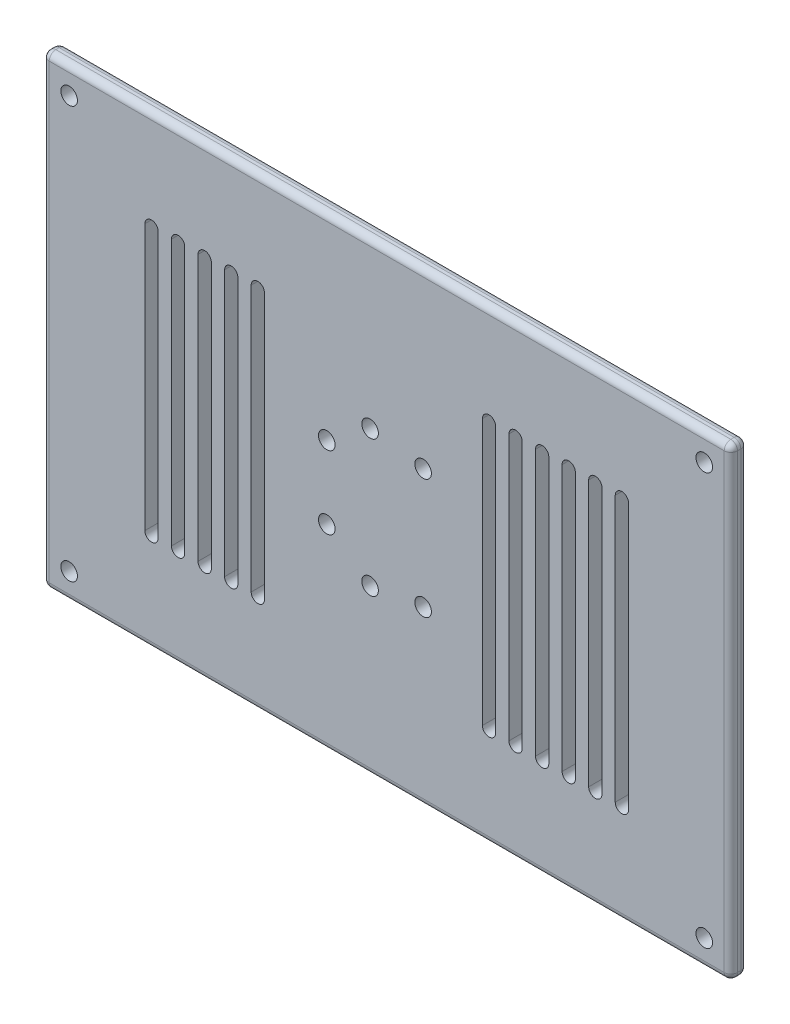
SolidWorks part; units mm, degrees
ref_plane "Plan de face" through (0, 0, 0) normal (0, 0, 1) x (1, 0, 0)
ref_plane "Plan de dessus" through (0, 0, 0) normal (0, 1, 0) x (1, 0, 0)
ref_plane "Plan de droite" through (0, 0, 0) normal (1, 0, 0) x (0, 0, -1)
sketch "Esquisse1" plane through (0, 0, 0) normal (0, 0, 1) x (1, 0, 0)
  line L1 (-51.8, 35) -> (51.8, 35)
  line L2 (-51.8, 35) -> (-51.8, -35)
  line L3 (-51.8, -35) -> (51.8, -35)
  line L4 (51.8, 35) -> (51.8, -35)
  line L5 (-51.8, 35) -> (51.8, -35) construction
  line L6 (-51.8, -35) -> (51.8, 35) construction
  point P0 (0, 0)
  point P5 (0, 0)
  point P13 (0, 0)
  dimension "D1" = 70
  dimension "D2" = 103.6
extrude "Boss.-Extru.1" add sketch "Esquisse1" along normal blind 2.5
sketch "Esquisse17" plane through (0, 0, 2.5) normal (0, 0, 1) x (1, 0, 0)
  line L1 (-2.5, 10.25) -> (2.5, 10.25)
  line L2 (-2.5, 10.25) -> (-2.5, -10.25) construction
  line L3 (-2.5, -10.25) -> (2.5, -10.25)
  line L4 (2.5, 10.25) -> (2.5, -10.25)
  line L5 (-2.5, 10.25) -> (2.5, -10.25) construction
  line L6 (-2.5, -10.25) -> (2.5, 10.25) construction
  circle A0 centre (-2.5, 10.25) radius 3
  circle A1 centre (-2.5, -10.25) radius 3
  point P0 (0, 0)
  point P9 (-2.5, -10.25)
  point P10 (-2.5, 10.25)
  dimension "D1" = 20.5
  dimension "D2" = 5
fillet "Congé3" radius 1 12 edges at (-51.8, 0, 2.5) (0, -35, 2.5) (0, 35, 2.5) (51.8, 0, 2.5) (51.8, -35, 1.25) (51.8, 35, 1.25) (-51.8, 35, 1.25) (-51.8, -35, 1.25) (51.8, 0, 0) (0, 35, 0) (-51.8, 0, 0) (0, -35, 0)
extrude "Boss.-Extru.12" add sketch "Esquisse17" against normal blind 7 contours A1 | A0
sketch "Esquisse40" plane through (0, 0, 2.5) normal (0, 0, 1) x (1, 0, 0)
  line L1 (9.0156, -5.4801) -> (5.4801, -9.0156)
  line L2 (9.0156, -5.4801) -> (-5.4801, 9.0156)
  line L3 (-5.4801, 9.0156) -> (-9.0156, 5.4801)
  line L4 (5.4801, -9.0156) -> (-9.0156, 5.4801)
  line L5 (2.5, -10.25) -> (-2.5, 10.25) construction
  line L6 (2.5, 10.25) -> (-2.5, -10.25) construction
  circle A0 centre (5.4801, -9.0156) radius 3
  circle A1 centre (-9.0156, 5.4801) radius 3
  point P0 (0, 0)
  dimension "D1" = 5
  dimension "D2" = 20.5
extrude "Boss.-Extru.8" add sketch "Esquisse40" against normal blind 7 contours A1 | A0
sketch "Esquisse42" plane through (0, 0, 2.5) normal (0, 0, 1) x (1, 0, 0)
  line L5 (-5.4801, -9.0156) -> (-9.0156, -5.4801)
  line L6 (-5.4801, -9.0156) -> (9.0156, 5.4801)
  line L7 (9.0156, 5.4801) -> (5.4801, 9.0156)
  line L8 (-9.0156, -5.4801) -> (5.4801, 9.0156)
  line L9 (2.5, -10.25) -> (-2.5, 10.25) construction
  line L10 (2.5, 10.25) -> (-2.5, -10.25) construction
  circle A0 centre (-9.0156, -5.4801) radius 3
  circle A1 centre (5.4801, 9.0156) radius 3
  point P0 (0, 0)
  dimension "D1" = 5
  dimension "D2" = 20.5
extrude "Boss.-Extru.10" add sketch "Esquisse42" against normal blind 7 contours A1 | A0
sketch "Esquisse36" plane through (0, 0, 2.5) normal (0, 0, 1) x (1, 0, 0)
  line L0 (25.4, 0) -> (0, 0) construction
  line L1 (50.8, -34) -> (50.8, 34) construction
  line L2 (50.8, 0) -> (25.4, 0) construction
  line L4 (35.4, -20) -> (15.4, -20) construction
  line L5 (35.4, -20) -> (35.4, 20) construction
  line L6 (35.4, 20) -> (15.4, 20) construction
  line L7 (15.4, -20) -> (15.4, 20) construction
  line L8 (35.4, -20) -> (15.4, 20) construction
  line L9 (35.4, 20) -> (15.4, -20) construction
  line L10 (35.4, 20) -> (35.4, -20) construction
  line L11 (36.4, 20) -> (36.4, -20)
  line L12 (34.4, 20) -> (34.4, -20)
  arc A0 (36.4, 20) -> (34.4, 20) centre (35.4, 20) ccw
  arc A1 (34.4, -20) -> (36.4, -20) centre (35.4, -20) ccw
  point P0 (25.4, 0)
  point P8 (35.4, 0)
  dimension "D1" = 20
  dimension "D2" = 40
extrude "Enlèv. mat.-Extru.2" cut sketch "Esquisse36" against normal through all
pattern_linear "Répétition linéaire1" count 6 spacing 4 along (-1, 0, 0) of "Enlèv. mat.-Extru.2"
sketch "Esquisse37" plane through (0, 0, 2.5) normal (0, 0, 1) x (1, 0, 0)
  line L0 (0, 0) -> (-50.8, 0) construction
  line L1 (-50.8, 34) -> (-50.8, -34) construction
  line L2 (-35.4, 20) -> (-35.4, -20) construction
  line L3 (-15.4, 20) -> (-35.4, 20) construction
  line L4 (-15.4, 20) -> (-15.4, -20) construction
  line L5 (-15.4, -20) -> (-35.4, -20) construction
  line L6 (-35.4, 20) -> (-35.4, -20) construction
  line L7 (-15.4, 20) -> (-35.4, -20) construction
  line L8 (-15.4, -20) -> (-35.4, 20) construction
  line L9 (-34.4, 20) -> (-34.4, -20)
  line L10 (-36.4, 20) -> (-36.4, -20)
  arc A0 (-34.4, 20) -> (-36.4, 20) centre (-35.4, 20) ccw
  arc A1 (-36.4, -20) -> (-34.4, -20) centre (-35.4, -20) ccw
  point P5 (-25.4, 0)
  point P11 (-35.4, 0)
  dimension "D1" = 40
  dimension "D2" = 20
extrude "Enlèv. mat.-Extru.3" cut sketch "Esquisse37" against normal through all
pattern_linear "Répétition linéaire2" count 5 spacing 4 along (1, 0, 0) of "Enlèv. mat.-Extru.3"
hole_wizard "Trou pour taraudage pour trou taraudé M38" positions "Esquisse3D10" profile "Esquisse41" hole size "M3" standard "AS"
sketch3d "Esquisse3D10"
  point P0 (5.4801, -9.0156, 2.5)
  point P3 (-9.0156, 5.4801, 2.5)
sketch "Esquisse41" plane through (5.4801, -9.0156, 2.5) normal (1, 0, 0) x (0, -1, 0)
  line L0 (0, 0) -> (0, 7.7511)
  line L1 (0, 7.7511) -> (1.25, 7)
  line L2 (1.25, 7) -> (1.25, 0)
  line L5 (1.25, 0) -> (0, 0)
  line L10 (0, 7.7511) -> (-1.25, 7) construction
  line L11 (0, -6.35) -> (0, 107.95) construction
  dimension "Diamètre du perçage" = 2.5
  dimension "Profondeur du perçage" = 7
  dimension "Angle de pointe" = 118
hole_wizard "Trou pour taraudage pour trou taraudé M39" positions "Esquisse3D11" profile "Esquisse43" hole size "M3" standard "AS"
sketch3d "Esquisse3D11"
  point P0 (5.4801, 9.0156, 2.5)
  point P3 (-9.0156, -5.4801, 2.5)
sketch "Esquisse43" plane through (5.4801, 9.0156, 2.5) normal (1, 0, 0) x (0, -1, 0)
  line L0 (0, 0) -> (0, 7.7511)
  line L1 (0, 7.7511) -> (1.25, 7)
  line L2 (1.25, 7) -> (1.25, 0)
  line L5 (1.25, 0) -> (0, 0)
  line L10 (0, 7.7511) -> (-1.25, 7) construction
  line L11 (0, -6.35) -> (0, 107.95) construction
  dimension "Diamètre du perçage" = 2.5
  dimension "Profondeur du perçage" = 7
  dimension "Angle de pointe" = 118
hole_wizard "Trou pour taraudage pour trou taraudé M311" positions "Esquisse3D15" profile "Esquisse47" hole size "M3" standard "AS"
sketch3d "Esquisse3D15"
  point P0 (-2.5, 10.25, 2.5)
  point P3 (-2.5, -10.25, 2.5)
sketch "Esquisse47" plane through (-2.5, 10.25, 2.5) normal (1, 0, 0) x (0, -1, 0)
  line L0 (0, 0) -> (0, 7.7511)
  line L1 (0, 7.7511) -> (1.25, 7)
  line L2 (1.25, 7) -> (1.25, 0)
  line L5 (1.25, 0) -> (0, 0)
  line L10 (0, 7.7511) -> (-1.25, 7) construction
  line L11 (0, -6.35) -> (0, 107.95) construction
  dimension "Diamètre du perçage" = 2.5
  dimension "Profondeur du perçage" = 7
  dimension "Angle de pointe" = 118
fillet "Congé4" radius 0.5 18 edges at (0.5, -10.25, 0) (0.5, -10.25, -4.5) (0.5, 10.25, 0) (0.5, 10.25, -4.5) (8.4801, -9.0156, -4.5) (8.4801, 9.0156, -4.5) (-6.0156, 5.4801, 0) (-6.0156, 5.4801, -4.5) (-6.0156, -5.4801, 0) (-6.0156, -5.4801, -4.5) (8.4801, 9.0156, 0) (8.4801, -9.0156, 0) (6.7301, -9.0156, -4.5) (6.7301, 9.0156, -4.5) (-1.25, -10.25, -4.5) (-1.25, 10.25, -4.5) (-7.7656, -5.4801, -4.5) (-7.7656, 5.4801, -4.5)
sketch "Esquisse48" plane through (0, 0, 2.5) normal (0, 0, 1) x (1, 0, 0)
  line L0 (51.8, 34) -> (51.8, -34) construction
  line L1 (-50.8, 35) -> (50.8, 35) construction
  line L2 (50.8, -35) -> (-50.8, -35) construction
  line L3 (-50.8, -35) -> (50.8, -35) construction
  line L6 (-51.8, -34) -> (-51.8, 34) construction
  circle A0 centre (-47.8, 31) radius 3
  circle A1 centre (-47.8, -31) radius 3
  circle A2 centre (47.8, 31) radius 3.3164
  circle A3 centre (47.8, -31) radius 3.4515
  dimension "D1" = 4
  dimension "D2" = 4
  dimension "D3" = 4
  dimension "D4" = 4
  dimension "D5" = 4
  dimension "D6" = 4
  dimension "D7" = 4
  dimension "D8" = 4
hole_wizard "Trou pour taraudage pour trou taraudé M312" positions "Esquisse3D16" profile "Esquisse49" hole size "M3" standard "AS"
sketch3d "Esquisse3D16"
  point P0 (-47.8, 31, 2.5)
  point P3 (-47.8, -31, 2.5)
  point P6 (47.8, -31, 2.5)
  point P9 (47.8, 31, 2.5)
sketch "Esquisse49" plane through (-47.8, 31, 2.5) normal (1, 0, 0) x (0, -1, 0)
  line L0 (0, 0) -> (0, 5.7511)
  line L1 (0, 5.7511) -> (1.25, 5)
  line L2 (1.25, 5) -> (1.25, 0)
  line L5 (1.25, 0) -> (0, 0)
  line L10 (0, 5.7511) -> (-1.25, 5) construction
  line L11 (0, -6.35) -> (0, 107.95) construction
  dimension "Diamètre du perçage" = 2.5
  dimension "Profondeur du perçage" = 5
  dimension "Angle de pointe" = 118
